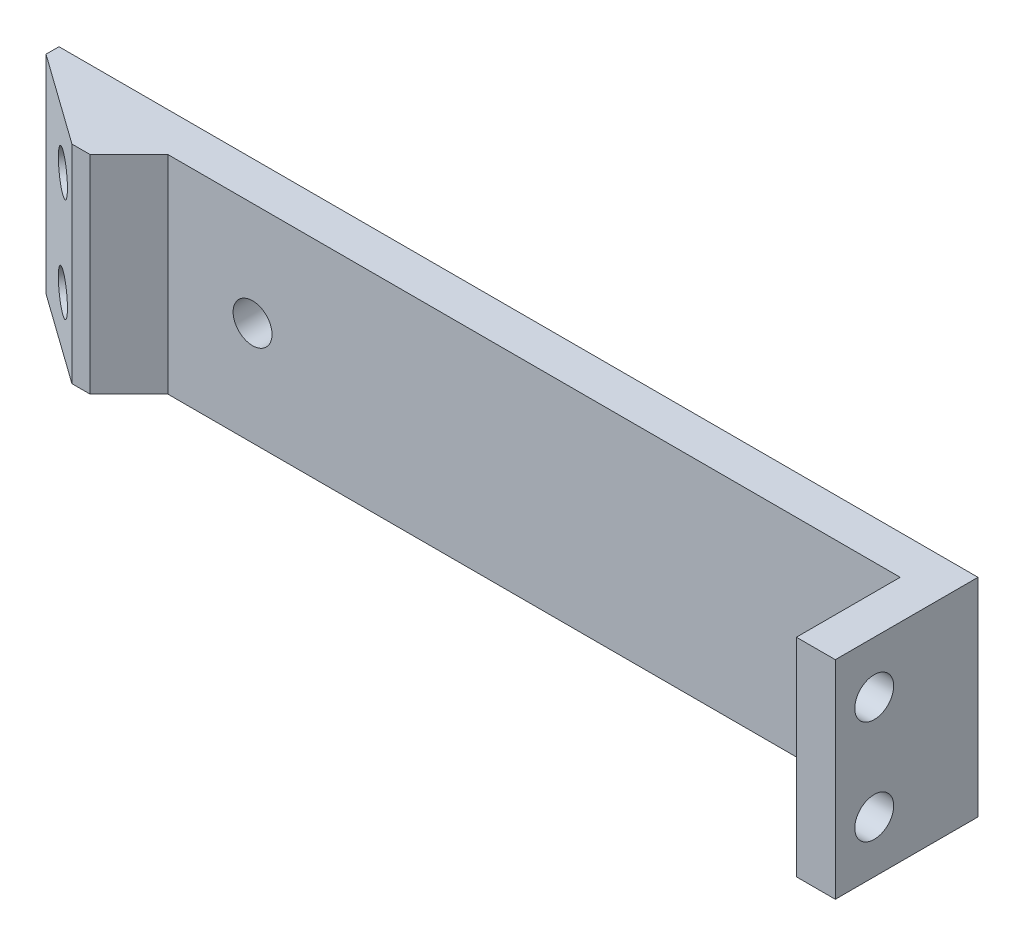
SolidWorks part; units mm, degrees
ref_plane "Front Plane" through (0, 0, 0) normal (0, 0, 1) x (1, 0, 0)
ref_plane "Top Plane" through (0, 0, 0) normal (0, 1, 0) x (1, 0, 0)
ref_plane "Right Plane" through (0, 0, 0) normal (1, 0, 0) x (0, 0, -1)
sketch "Sketch1" plane through (0, 0, 0) normal (0, 0, 1) x (1, 0, 0)
  line L1 (-35.425, -8) -> (35.425, -8)
  line L2 (-35.425, -8) -> (-35.425, 8)
  line L3 (-35.425, 8) -> (35.425, 8)
  line L4 (35.425, -8) -> (35.425, 8)
  line L5 (-35.425, -8) -> (35.425, 8) construction
  line L6 (-35.425, 8) -> (35.425, -8) construction
  point P0 (0, 0)
  dimension "D1" = 70.85
  dimension "D2" = 16
extrude "Boss-Extrude1" add sketch "Sketch1" along normal blind 3
sketch "Sketch2" plane through (0, 0, 3) normal (0, 0, 1) x (1, 0, 0)
  line L0 (-35.425, -8) -> (35.425, -8) construction
  line L1 (-35.425, 8) -> (-27.025, 8)
  line L2 (-35.425, 8) -> (-35.425, -8)
  line L3 (-35.425, -8) -> (-27.025, -8)
  line L4 (-27.025, 8) -> (-27.025, -8)
  dimension "D1" = 8.4
extrude "Boss-Extrude2" add sketch "Sketch2" along normal blind 3
chamfer "Chamfer1" distance 5 distance2 7 1 edges at (-35.425, 0, 6) first distance on face at (-35.425, 0, 3)
sketch "Sketch3" plane through (-12.4409, 0, 17.4172) normal (-0.5812, 0, 0.8137) x (0.8137, 0, 0.5812)
  line L0 (-28.2453, 8) -> (-19.6429, 8) construction
  line L1 (-19.6429, -8) -> (-28.2453, -8) construction
  line L2 (-19.6429, 8) -> (-19.6429, -8) construction
  circle A0 centre (-22.6429, 4) radius 1.5
  circle A1 centre (-22.6429, -4) radius 1.5
  dimension "D1" = 3
  dimension "D2" = 3
  dimension "D3" = 4
  dimension "D4" = 4
  dimension "D6" = 3
  dimension "D5" = 3
extrude "Cut-Extrude1" cut sketch "Sketch3" against normal blind 3
chamfer "Chamfer2" distance 3 angle 45 1 edges at (-27.025, 0, 3)
sketch "Sketch4" plane through (-12.4409, 0, 17.4172) normal (-0.5812, 0, 0.8137) x (0.8137, 0, 0.5812)
  line L1 (-19.4675, 4) -> (-21.0552, 6.75)
  line L2 (-21.0552, 6.75) -> (-24.2307, 6.75)
  line L3 (-24.2307, 6.75) -> (-25.8184, 4)
  line L4 (-25.8184, 4) -> (-24.2307, 1.25)
  line L5 (-24.2307, 1.25) -> (-21.0552, 1.25)
  line L6 (-21.0552, 1.25) -> (-19.4675, 4)
  line L7 (-19.4675, -4) -> (-21.0552, -1.25)
  line L8 (-21.0552, -1.25) -> (-24.2307, -1.25)
  line L9 (-24.2307, -1.25) -> (-25.8184, -4)
  line L10 (-25.8184, -4) -> (-24.2307, -6.75)
  line L11 (-24.2307, -6.75) -> (-21.0552, -6.75)
  line L12 (-21.0552, -6.75) -> (-19.4675, -4)
  circle A0 centre (-22.6429, 4) radius 2.75 construction
  circle A1 centre (-22.6429, -4) radius 2.75 construction
  dimension "D1" = 5.5
  dimension "D2" = 5.5
extrude "Cut-Extrude2" cut sketch "Sketch4" against normal blind 8 from offset 3 offset against normal yes
sketch "Sketch5" plane through (0, 0, 3) normal (0, 0, 1) x (1, 0, 0)
  line L0 (-24.025, -8) -> (35.425, -8) construction
  line L1 (35.425, 8) -> (32.425, 8)
  line L2 (35.425, 8) -> (35.425, -8)
  line L3 (35.425, -8) -> (32.425, -8)
  line L4 (32.425, 8) -> (32.425, -8)
  dimension "D1" = 3
extrude "Boss-Extrude3" add sketch "Sketch5" along normal blind 8
sketch "Sketch6" plane through (35.425, 0, 0) normal (1, 0, 0) x (0, 0, -1)
  line L0 (-11, -8) -> (-11, 8) construction
  line L1 (-11, 8) -> (0, 8) construction
  line L2 (-11, -8) -> (0, -8) construction
  circle A0 centre (-8, 4) radius 1.5
  circle A1 centre (-8, -4) radius 1.5
  dimension "D1" = 3
  dimension "D2" = 3
  dimension "D3" = 3
  dimension "D4" = 3
  dimension "D5" = 4
  dimension "D6" = 4
extrude "Cut-Extrude3" cut sketch "Sketch6" against normal blind 8
sketch "Sketch7" plane through (0, 0, 0) normal (0, 0, -1) x (-1, 0, 0)
  circle A0 centre (17.5, 0) radius 1.5
  dimension "D1" = 3
  dimension "D2" = 17.5
extrude "Cut-Extrude4" cut sketch "Sketch7" against normal blind 10
